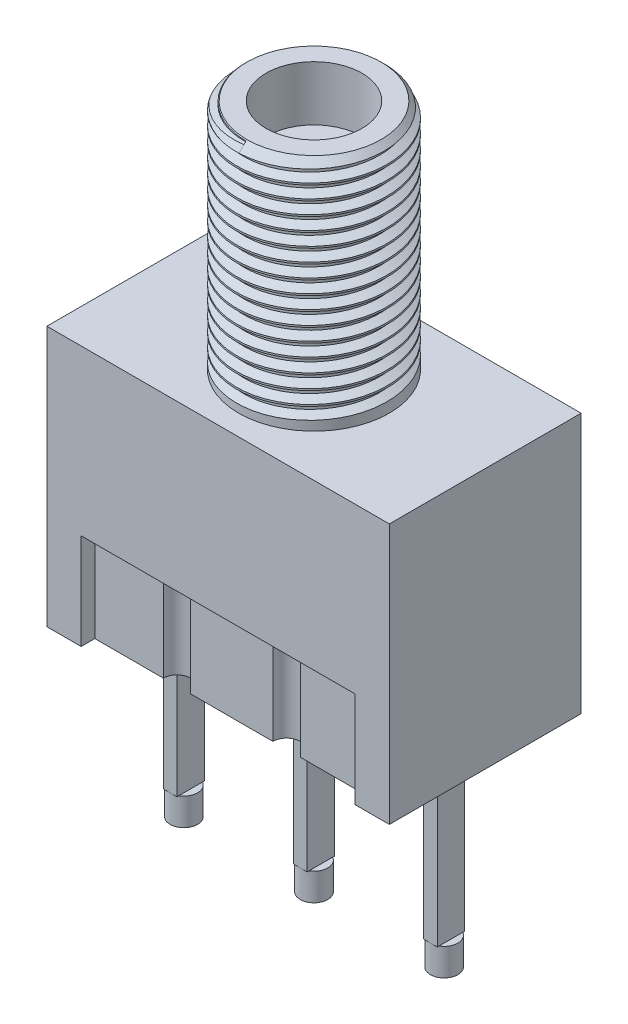
SolidWorks part; units mm, degrees
ref_plane "Front" through (0, 0, 0) normal (0, 0, 1) x (1, 0, 0)
ref_plane "Top" through (0, 0, 0) normal (0, 1, 0) x (1, 0, 0)
ref_plane "Right" through (0, 0, 0) normal (1, 0, 0) x (0, 0, -1)
sketch "Sketch1" plane through (0, 0, 0) normal (0, 1, 0) x (1, 0, 0)
  line L0 (0, 0.4087) -> (0, 3.9087) construction
  line L1 (0, 0.4087) -> (6.25, 0.4087) construction
  line L3 (-6.25, 3.9087) -> (6.25, 3.9087)
  line L4 (-6.25, 3.9087) -> (-6.25, -3.0913)
  line L5 (-6.25, -3.0913) -> (6.25, -3.0913)
  line L6 (6.25, 3.9087) -> (6.25, -3.0913)
  dimension "D1" = 12.5
  dimension "D2" = 7
extrude "Boss-Extrude1" add sketch "Sketch1" along normal blind 9.5
sketch "Sketch2" plane through (0, 0, 0) normal (0, -1, 0) x (1, 0, 0)
  line L0 (0, 3.0913) -> (0, -3.9087) construction
  line L1 (-6.25, 3.0913) -> (6.25, 3.0913) construction
  line L2 (-5, 3.0913) -> (5, 3.0913)
  line L3 (-5, 3.0913) -> (-5, 2.5913)
  line L4 (-5, 2.5913) -> (-2.5, 2.5913)
  line L5 (5, 3.0913) -> (5, 2.5913)
  line L6 (-6.25, -0.4087) -> (6.25, -0.4087) construction
  line L7 (-5, -3.9087) -> (5, -3.9087)
  line L8 (-5, -3.9087) -> (-5, -3.4087)
  line L9 (5, -3.9087) -> (5, -3.4087)
  line L10 (-5, -3.4087) -> (-2.5, -3.4087)
  line L11 (-2, -3.4087) -> (-2, 2.5913) construction
  line L12 (-1.5, -3.4087) -> (1.5, -3.4087)
  line L13 (-1.5, 2.5913) -> (1.5, 2.5913)
  line L14 (2.5, 2.5913) -> (5, 2.5913)
  line L15 (2.5, -3.4087) -> (5, -3.4087)
  arc A0 (-1.5, -3.4087) -> (-2.5, -3.4087) centre (-2, -3.4087) ccw
  arc A1 (-1.5, 2.5913) -> (-2.5, 2.5913) centre (-2, 2.5913) cw
  arc A2 (1.5, 2.5913) -> (2.5, 2.5913) centre (2, 2.5913) ccw
  arc A3 (1.5, -3.4087) -> (2.5, -3.4087) centre (2, -3.4087) cw
  dimension "D4" = 0.5
  dimension "D1" = 5
  dimension "D2" = 5
  dimension "D3" = 0.5
  dimension "D5" = 2
extrude "Cut-Extrude1" cut sketch "Sketch2" against normal blind 3.5
sketch "Sketch3" plane through (0, 0, 0) normal (0, -1, 0) x (1, 0, 0)
  line L0 (-6.25, -0.4087) -> (6.25, -0.4087) construction
  line L2 (6.25, 3.0913) -> (6.25, -3.9087) construction
  line L3 (0, -3.4087) -> (0, 2.5913) construction
  line L5 (-1.5, 2.5913) -> (1.5, 2.5913) construction
  line L6 (1.5, -3.4087) -> (-1.5, -3.4087) construction
  line L7 (-2.5, 1.0913) -> (-1.5, 1.0913)
  line L8 (-2.5, 1.0913) -> (-2.5, -1.9087)
  line L9 (-2.5, -1.9087) -> (-1.5, -1.9087)
  line L10 (-1.5, 1.0913) -> (-1.5, -1.9087)
  line L11 (-6.25, -3.9087) -> (-6.25, 3.0913) construction
  line L12 (2.5, -1.9087) -> (1.5, -1.9087)
  line L13 (1.5, 1.0913) -> (1.5, -1.9087)
  line L14 (2.5, 1.0913) -> (1.5, 1.0913)
  line L15 (2.5, 1.0913) -> (2.5, -1.9087)
  point P13 (6.25, -0.4087)
  point P17 (-6.25, -0.4087)
  point P18 (-2.5, -0.4087)
  point P19 (0, 2.5913)
  point P22 (0, -3.4087)
  dimension "D1" = 1
  dimension "D2" = 1.5
  dimension "D3" = 3
extrude "Boss-Extrude2" add sketch "Sketch3" along normal blind 1
sketch "Sketch4" plane through (0, 0, 0) normal (0, -1, 0) x (1, 0, 0)
  line L0 (-6.25, -0.4087) -> (6.25, -0.4087) construction
  line L1 (-6.25, -3.9087) -> (-6.25, 3.0913) construction
  line L2 (6.25, 3.0913) -> (6.25, -3.9087) construction
  line L5 (-1.5, 2.5913) -> (1.5, 2.5913) construction
  line L7 (0, 2.5913) -> (0, -3.4087) construction
  line L8 (-5, 0.0913) -> (-4.5, 0.0913)
  line L9 (-5, 0.0913) -> (-5, -0.9087)
  line L10 (-5, -0.9087) -> (-4.5, -0.9087)
  line L11 (-4.5, 0.0913) -> (-4.5, -0.9087)
  line L12 (4.5, 0.0913) -> (4.5, -0.9087)
  line L13 (-0.25, 0.0913) -> (0.25, 0.0913)
  line L14 (-0.25, 0.0913) -> (-0.25, -0.9087)
  line L15 (-0.25, -0.9087) -> (0.25, -0.9087)
  line L16 (0.25, 0.0913) -> (0.25, -0.9087)
  line L17 (5, -0.9087) -> (4.5, -0.9087)
  line L18 (5, 0.0913) -> (4.5, 0.0913)
  line L19 (5, 0.0913) -> (5, -0.9087)
  line L21 (1.5, -3.4087) -> (-1.5, -3.4087) construction
  point P4 (-6.25, -0.4087)
  point P7 (6.25, -0.4087)
  point P28 (0, 2.5913)
  point P31 (0, -3.4087)
  dimension "D1" = 0.5
  dimension "D2" = 0.5
  dimension "D3" = 0.5
  dimension "D4" = 1.25
  dimension "D5" = 0.5
  dimension "D6" = 0.5
  dimension "D7" = 0.5
  dimension "D8" = 6
extrude "Boss-Extrude3" add sketch "Sketch4" along normal blind 6
sketch "Sketch5" plane through (0, 9.5, 0) normal (0, 1, 0) x (1, 0, 0)
  line L2 (6.25, 3.9087) -> (-6.25, 3.9087) construction
  line L5 (-6.25, 3.9087) -> (-6.25, -3.0913) construction
  circle A0 centre (0, 0.4087) radius 2.75
  dimension "D1" = 5.5
  dimension "D2" = 3.5
  dimension "D3" = 6.25
extrude "Boss-Extrude4" add sketch "Sketch5" along normal blind 8.5
sketch "Sketch6" plane through (0, 18, 0) normal (0, 1, 0) x (1, 0, 0)
  circle A1 centre (0, 0.4087) radius 2.4795
  dimension "D1" = 4.959
curve "Helix/Spiral1" pitch 0.5 height 8.125 radius 2.4795 centre (0, 18, -0.4087) axis (0, -1, 0) start towards (0, 0, 1)
sketch "Sketch8" plane through (0, 0, 0) normal (1, 0, 0) x (0, 0, -1)
  line L0 (-2.0708, 16) -> (-2.0708, 19.2271) construction
  line L1 (-2.0708, 18) -> (-3.0145, 18) construction
  line L2 (-2.0708, 17.5) -> (-3.0145, 17.5) construction
  line L3 (-2.0708, 17.5) -> (-1.4984, 17.5) construction
  line L4 (-1.4984, 18.5) -> (-2.9633, 18.5) construction
  line L5 (-2.0708, 18) -> (-1.4984, 18) construction
  line L6 (-2.3415, 18.7523) -> (-2.3415, 16.8073) construction
  line L7 (-2.0708, 18.0625) -> (-2.3415, 18.2187)
  line L8 (-2.0708, 17.9375) -> (-2.3415, 17.7813)
  line L9 (-2.0708, 18.0625) -> (-2.0708, 17.9375)
  line L10 (-2.0708, 18.0625) -> (-1.9626, 18) construction
  line L11 (-1.9626, 18) -> (-2.0708, 17.9375) construction
  line L12 (-2.3415, 18.2187) -> (-2.5919, 18.2187)
  line L13 (-2.5919, 18.2187) -> (-2.5919, 17.7813)
  line L14 (-2.5919, 17.7813) -> (-2.3415, 17.7813)
  point P14 (-2.0708, 18.0625)
  point P16 (-2.0708, 17.9375)
  dimension "D1" = 0.5
  dimension "D2" = 0.2706
  dimension "D3" = 0.5
  dimension "D4" = 60
  dimension "D5" = 30
  dimension "D6" = 0.1083
chamfer "Chamfer1" distance 0.3 angle 45 1 edges at (0, 18, 2.3413)
sweep "Cut-Sweep2" cut profiles "Sketch8" path "Helix/Spiral1"
sketch "Sketch9" plane through (0, 0, -0.4087) normal (0, 0, 1) x (1, 0, 0)
  line L0 (-2.7501, 10.0937) -> (-2.7501, 9.6563) construction
  line L1 (-2.7501, 10.0937) -> (-2.4795, 9.9375) construction
  line L2 (-2.4795, 9.9375) -> (-2.4795, 9.8125) construction
  line L3 (-2.4795, 9.8125) -> (-2.7501, 9.6563) construction
  line L4 (-2.7501, 10.0937) -> (-2.7501, 9.6563)
  line L5 (-2.7501, 10.0937) -> (-2.4795, 9.9375)
  line L6 (-2.4795, 9.9375) -> (-2.4795, 9.8125)
  line L7 (-2.4795, 9.8125) -> (-2.7501, 9.6563)
extrude "Cut-Extrude2" cut sketch "Sketch9" against normal blind 2.8
sketch "Sketch11" plane through (0, 18, 0) normal (0, 1, 0) x (1, 0, 0)
  circle A0 centre (0, 0.4087) radius 1.75
  dimension "D1" = 3.5
extrude "Cut-Extrude3" cut sketch "Sketch11" against normal blind 2 contours A0
sketch "Sketch12" plane through (0, 0, 0) normal (0, 0, 1) x (1, 0, 0)
  line L0 (0, 17.7) -> (0, 9.5) construction
  point P0 (0, 16.1983)
ref_plane "Plane1" through (0, 0, 0) normal (-1, 0, 0) x (0, 0, 1)
sketch "Sketch13" plane through (0, 0, 0) normal (-1, 0, 0) x (0, 0, 1)
  line L0 (0, 16.1983) -> (-0.4201, 16.1983) construction
ref_axis "Axis1" through (0, 16.1983, 0) along (0, 0, -1)
sketch "Sketch14" plane through (0, 18, 0) normal (0, 1, 0) x (1, 0, 0)
  line L0 (0, 0.4087) -> (2.75, 0.4087) construction
  line L2 (2.75, -0.0913) -> (2.25, -0.0913)
  line L3 (2.75, -0.0913) -> (2.75, 0.9087)
  line L4 (2.75, 0.9087) -> (2.25, 0.9087)
  line L5 (2.25, -0.0913) -> (2.25, 0.9087)
  line L6 (2.75, -0.0913) -> (2.25, 0.9087) construction
  line L7 (2.75, 0.9087) -> (2.25, -0.0913) construction
  point P2 (3.2835, 0.4087)
  dimension "D2" = 0.5
  dimension "D3" = 1
  dimension "D4" = 0.5
  dimension "D5" = 2.75
sketch "Sketch15" plane through (0, -6, 0) normal (0, -1, 0) x (1, 0, 0)
  circle A0 centre (0, -0.4087) radius 0.5
  circle A1 centre (4.75, -0.4087) radius 0.5
  circle A2 centre (-4.75, -0.4087) radius 0.5
extrude "Boss-Extrude5" add sketch "Sketch15" along normal blind 1
